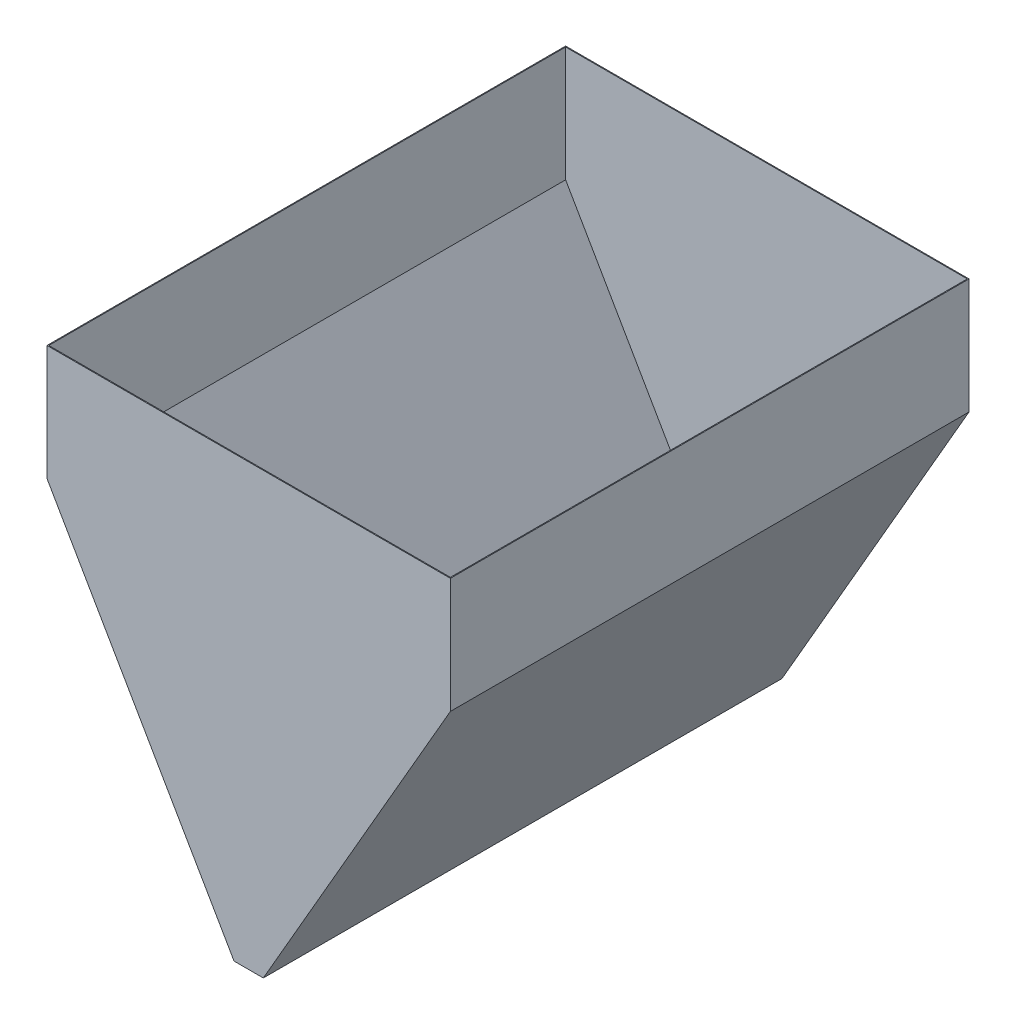
SolidWorks part; units mm, degrees
material "AISI 304"
ref_plane "Alzado" through (0, 0, 0) normal (0, 0, 1) x (1, 0, 0)
ref_plane "Planta" through (0, 0, 0) normal (0, 1, 0) x (1, 0, 0)
ref_plane "Vista lateral" through (0, 0, 0) normal (1, 0, 0) x (0, 0, -1)
sketch "Croquis1" plane through (0, 0, 0) normal (0, 1, 0) x (1, 0, 0)
  line L1 (-175, 225) -> (175, 225)
  line L2 (-175, 225) -> (-175, -225)
  line L3 (-175, -225) -> (175, -225)
  line L4 (175, 225) -> (175, -225)
  line L5 (-175, 225) -> (175, -225) construction
  line L6 (-175, -225) -> (175, 225) construction
  point P0 (0, 0)
  dimension "D1" = 350
  dimension "D2" = 450
ref_plane "Plano1" through (0, -281.458, 0) normal (0, 1, 0) x (1, 0, 0)
sketch "Croquis2" plane through (0, -281.458, 0) normal (0, 1, 0) x (1, 0, 0)
  line L1 (-12.7, 225) -> (12.7, 225)
  line L2 (-12.7, 225) -> (-12.7, -225)
  line L3 (-12.7, -225) -> (12.7, -225)
  line L4 (12.7, 225) -> (12.7, -225)
  line L5 (-12.7, 225) -> (12.7, -225) construction
  line L6 (-12.7, -225) -> (12.7, 225) construction
  line L7 (175, 225) -> (175, -225) construction
  point P0 (0, 0)
  dimension "D1" = 25.4
loft "Recubrir1" add profiles "Croquis1", "Croquis2" connector at (-175, 0, -225) connector at (-12.7, -281.458, -225)
sketch "Croquis3" plane through (0, 0, 0) normal (0, 1, 0) x (1, 0, 0)
  line L1 (-175, 225) -> (175, 225)
  line L2 (-175, 225) -> (-175, -225)
  line L3 (-175, -225) -> (175, -225)
  line L4 (175, 225) -> (175, -225)
extrude "Saliente-Extruir1" add sketch "Croquis3" along normal blind 100
shell "Vaciado2" thickness 0.76 removed face at (0, -281.458, 0) removed face at (0, 100, 0)
